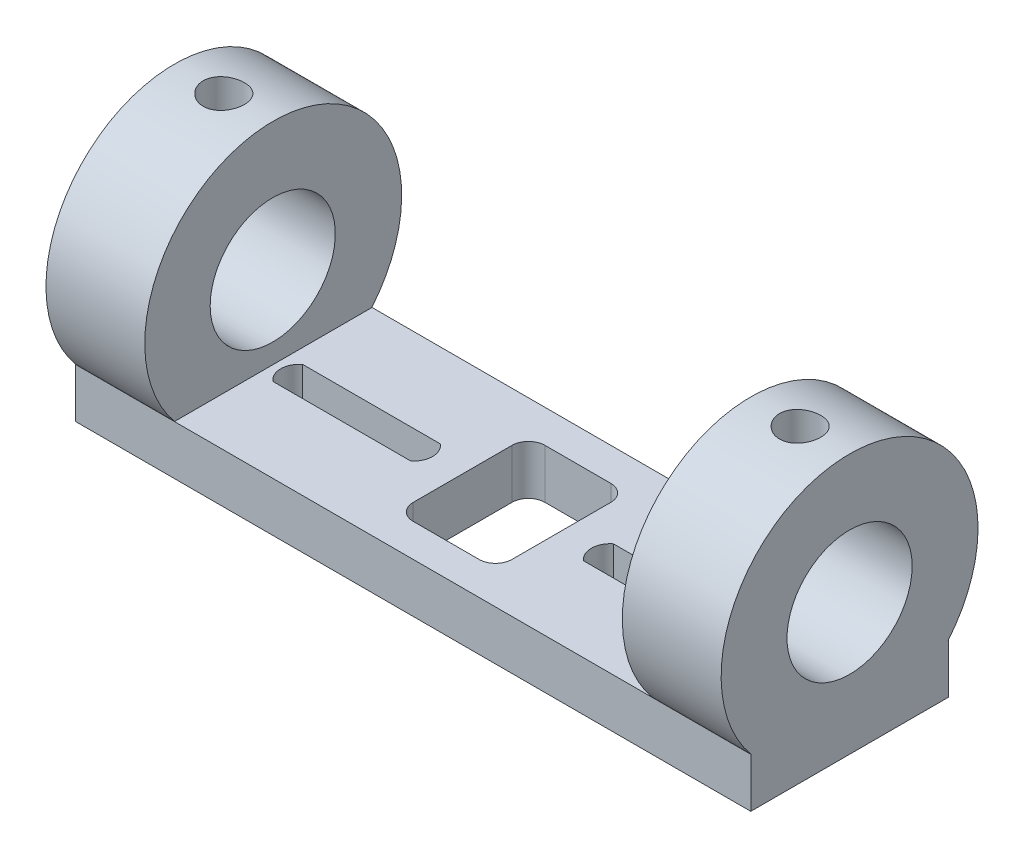
SolidWorks part; units mm, degrees
ref_plane "前视基准面" through (0, 0, 0) normal (0, 0, 1) x (1, 0, 0)
ref_plane "上视基准面" through (0, 0, 0) normal (0, 1, 0) x (1, 0, 0)
ref_plane "右视基准面" through (0, 0, 0) normal (1, 0, 0) x (0, 0, -1)
sketch "草图1" plane through (0, 0, 0) normal (0, 1, 0) x (1, 0, 0)
  line L5 (15.5, 6) -> (15.5, -6)
  line L7 (-15.5, -6) -> (-15.5, 6)
  line L8 (-18, 6) -> (18, 6)
  line L9 (3, 3) -> (3, -3)
  line L10 (-18, -6) -> (18, -6)
  line L11 (-3, -3) -> (-3, 3)
  line L13 (2, 4) -> (-2, 4)
  line L15 (-2, -4) -> (2, -4)
  line L18 (0, -13.7153) -> (0, 13.7153) construction
  line L20 (-18, 6) -> (-20.5, 6)
  line L24 (-20.5, 6) -> (-20.5, -6)
  line L25 (-20.5, -6) -> (-18, -6)
  line L26 (18, -6) -> (20.5, -6)
  line L27 (20.5, -6) -> (20.5, 6)
  line L28 (20.5, 6) -> (18, 6)
  line L35 (13.6158, 0.9) -> (5.2548, 0.9)
  line L36 (-13.6158, -0.9) -> (-5.2548, -0.9)
  line L37 (-13.6158, 0.9) -> (-5.2548, 0.9)
  line L38 (13.6158, -0.9) -> (5.2548, -0.9)
  arc A1 (-5.2548, 0.9) -> (-5.2548, -0.9) centre (-5.9707, 0) cw
  arc A4 (2, -4) -> (3, -3) centre (2, -3) ccw
  arc A5 (-2, -4) -> (-3, -3) centre (-2, -3) cw
  arc A6 (3, 3) -> (2, 4) centre (2, 3) ccw
  arc A7 (-3, 3) -> (-2, 4) centre (-2, 3) cw
  arc A8 (-13.6158, 0.9) -> (-13.6158, -0.9) centre (-12.8999, 0) ccw
  arc A11 (5.2548, 0.9) -> (5.2548, -0.9) centre (5.9707, 0) ccw
  arc A12 (13.6158, 0.9) -> (13.6158, -0.9) centre (12.8999, 0) cw
  point P0 (0, 0)
  point P20 (0, 0)
  dimension "D1" = 1
extrude "凸台-拉伸1" add sketch "草图1" along normal blind 3 contours L10 L18 L15 A5 L11 A7 L13 L8 L7 A8 A1 | L24 L25 L10 L7 L8 L20 | L18 L10 L5 L8 L13 A6 L9 A4 L15 | L27 L28 L8 L5 L10 L26 region at (18, 0, 0) region at (15.304, 0, 0) region at (-0.196, 0, -5) region at (-18, 0, 0)
sketch "草图2" plane through (-18, 0, 0) normal (-1, 0, 0) x (0, 0, 1)
  circle A0 centre (0.0291, 7.9938) radius 3.8
  circle A1 centre (0, 8) radius 7.8
extrude "凸台-拉伸2" add sketch "草图2" against normal blind 3.5 and the other way blind 2.5
sketch "草图4" plane through (20.5, 0, 0) normal (1, 0, 0) x (0, 0, -1)
  circle A0 centre (0, 8) radius 3.8
  circle A1 centre (0, 8) radius 7.8
extrude "凸台-拉伸3" add sketch "草图4" against normal blind 6
ref_axis "基准轴1" through (-20.5, 7.9938, 0.0291) along (1, 0, 0)
ref_plane "基准面4" through (0, 7.9938, 0) normal (0, 1, 0) x (1, 0, 0)
sketch "草图7" plane through (0, 7.9938, 0) normal (0, 1, 0) x (1, 0, 0)
  circle A0 centre (-17.5, 0) radius 1.25
  circle A1 centre (17.5, 0) radius 1.25
extrude "切除-拉伸1" cut sketch "草图7" along normal blind 16
